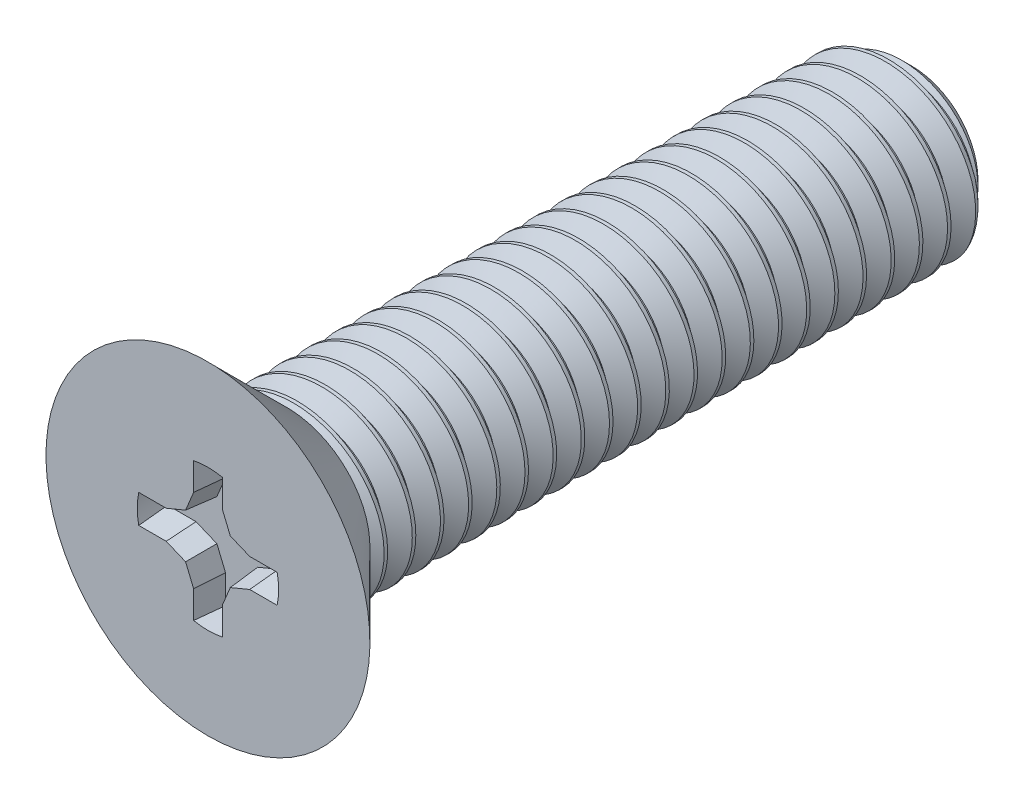
SolidWorks part; units mm, degrees
ref_plane "Front Plane" through (0, 0, 0) normal (0, 0, 1) x (1, 0, 0)
ref_plane "Top Plane" through (0, 0, 0) normal (0, 1, 0) x (1, 0, 0)
ref_plane "Right Plane" through (0, 0, 0) normal (1, 0, 0) x (0, 0, -1)
sketch "Sketch1" plane through (0, 0, 0) normal (1, 0, 0) x (0, 0, -1)
  line L0 (0, 0) -> (-2.5, 0) construction
  line L1 (-2.5, 4.6) -> (-2.5, -4.6) construction
  line L2 (-2.5, 4.6) -> (0, 2.1) construction
  line L3 (-2.5, -4.6) -> (0, -2.1) construction
  line L4 (0, 2.5) -> (0, -2.5) construction
  line L5 (0, 0) -> (17.5, 0) construction
  line L6 (0, 2.5) -> (0.8, 2.5) construction
  line L7 (0, 2.5) -> (-0.4, 2.5) construction
  line L8 (17.5, 2.1) -> (17.5, -2.1) construction
  point P6 (-2.5, 0)
  point P11 (0, 0)
  point P16 (-0.4, 2.5)
  point P17 (14.7, -2.5)
  point P20 (17.5, 0)
  point P21 (-1.25, 0)
  point P22 (14.7, -2.1)
  point P23 (17.5, -2.1)
  point P25 (17.5, 2.1)
  dimension "Head Height" = 2.5
  dimension "Head Diameter" = 9.2
  dimension "Countersink Angle" = 90
  dimension "Thread OD" = 5
  dimension "Length" = 20
  dimension "Thread Pitch" = 0.8
  dimension "D1" = 2.8
sketch "Sketch2" plane through (0, 0, 0) normal (0, 0, 1) x (1, 0, 0)
  line L0 (0.4064, 2.0066) -> (-0.4064, 2.0066) construction
  circle A0 centre (0, 0) radius 2.0066 construction
  point P3 (0, 2.0066)
  point P7 (0, 2.0066)
  dimension "Drive Dia" = 4.0132
  dimension "Drive Width" = 0.8128
sketch "Sketch3" plane through (0, 0, 0) normal (1, 0, 0) x (0, 0, -1)
  line L0 (-2.5, 0) -> (-2.5, 4.6)
  line L1 (-2.5, 4.6) -> (-0.4, 2.5)
  line L2 (-2.5, 4.6) -> (0, 2.1) construction
  line L3 (0, 2.5) -> (0.8, 2.5) construction
  line L4 (-2.5, 0) -> (-0.4, 0)
  line L5 (0, 0) -> (-2.5, 0) construction
  line L6 (-0.4, 0) -> (-0.4, 2.5)
revolve "Revolve1" add sketch "Sketch3" angle 360 about L4
sketch "Sketch5" plane through (0, 0, 0) normal (1, 0, 0) x (0, 0, -1)
  line L0 (17.5, 0) -> (-0.4, 0)
  line L1 (0, 0) -> (17.5, 0) construction
  line L2 (-0.4, 0) -> (-0.4, 2.5)
  line L3 (-0.4, 2.5) -> (16.868, 2.5)
  line L4 (16.868, 2.5) -> (17.5, 1.868)
  line L5 (17.5, 1.868) -> (17.5, 0)
  line L6 (16.868, 2.5) -> (17.5, 2.5) construction
  line L7 (17.5, 2.5) -> (17.5, 1.868) construction
  line L8 (0, 2.5) -> (0.8, 2.5) construction
  line L9 (-0.4, -2.5) -> (-0.4, 2.5) construction
  dimension "D1" = 0.632
revolve "Revolve2" add sketch "Sketch5" angle 360 about L0
sketch "Sketch4" plane through (0, 0, 2.5) normal (0, 0, 1) x (1, 0, 0)
  line L0 (0, 0) -> (0, 2.0066)
  line L1 (0, 0) -> (2.0066, 0)
  line L2 (0, 0) -> (1.1857, 1.1857) construction
  line L3 (0.4064, 1.965) -> (0.4064, 1.1857)
  line L4 (0.4064, 1.1857) -> (0.4064, 0.4064) construction
  line L5 (1.1857, 0.4064) -> (0.4064, 0.4064) construction
  line L6 (1.965, 0.4064) -> (1.1857, 0.4064)
  line L7 (0.4064, 1.1857) -> (0.6347, 0.6347)
  line L8 (0.6347, 0.6347) -> (1.1857, 0.4064)
  line L9 (0, 2.0066) -> (0, 4.6) construction
  line L10 (0, 4.6) -> (0, -4.6) construction
  circle A0 centre (0, 0) radius 2.0066 construction
  arc A1 (0, 2.0066) -> (0.4064, 1.965) centre (0, 0) cw
  arc A2 (2.0066, 0) -> (1.965, 0.4064) centre (0, 0) ccw
  arc A3 (1.1857, 0.4064) -> (0.4064, 1.1857) centre (1.1857, 1.1857) cw construction
  circle A4 centre (0, 0) radius 4.6 construction
  point P8 (0.6347, 0.6347)
  point P22 (0, -2.0066)
  point P23 (0, 2.0066)
  dimension "D1" = 2.5934
extrude "Cut-Extrude1" cut sketch "Sketch4" against normal blind 0.8333 contours L1 A2 L6 L8 L7 L3 A1 L0
pattern_circular "CirPattern1" count 4 over 360 about axis through (0, 0, 0) along (0, 0, 1) of "Cut-Extrude1"
draft "Draft2" type of draft neutral plane draft angle 5 faces to draft 16 face at (-1.5754, 0.4064, 2.0833) face at (-0.9102, 0.5205, 2.0833) face at (-0.5205, 0.9102, 2.0833) face at (-0.4064, 1.5754, 2.0833) face at (0.4064, 1.5754, 2.0833) face at (0.5205, 0.9102, 2.0833) face at (0.9102, 0.5205, 2.0833) face at (1.5754, 0.4064, 2.0833) face at (1.5754, -0.4064, 2.0833) face at (0.9102, -0.5205, 2.0833) face at (0.5205, -0.9102, 2.0833) face at (0.4064, -1.5754, 2.0833) face at (-0.4064, -1.5754, 2.0833) face at (-0.5205, -0.9102, 2.0833) face at (-0.9102, -0.5205, 2.0833) face at (-1.5754, -0.4064, 2.0833) neutral plane through (0, 0, 2.5) neutral plane normal (0, 0, 1) parameters "D1"=5
ref_plane "Plane1" through (0, 0, 0.4) normal (0, 0, -1) x (-1, 0, 0)
split "Split1" trim tools "Plane1" bodies to split 107 105 resulting bodies 108 109
sketch "Sketch6" plane through (0, 0, -17.5) normal (0, 0, 1) x (1, 0, 0)
  circle A1 centre (0, 0) radius 2.5
  circle A2 centre (0, 0) radius 2.5
  dimension "D1" = 0
curve "Helix/Spiral1" pitch 0.8 height 20 turns 25
sketch "Sketch7" plane through (0, 0, 0) normal (1, 0, 0) x (0, 0, -1)
  line L0 (17.45, 2.5866) -> (18.25, 2.5866) construction
  line L1 (17.45, 2.5866) -> (17.85, 1.8938) construction
  line L2 (17.85, 1.8938) -> (18.25, 2.5866) construction
  line L3 (17.8, 1.9804) -> (17.9, 1.9804) construction
  line L4 (17.5, 2.5) -> (18.2, 2.5) construction
  line L5 (17.85, 2.5) -> (17.85, 2.5866) construction
  line L6 (17.85, 1.9804) -> (17.85, 1.8938) construction
  line L7 (17.85, 2.5433) -> (17.475, 2.5433) construction
  line L10 (17.9, 1.9804) -> (17.8, 1.9804)
  line L11 (17.475, 2.5433) -> (17.8, 1.9804)
  line L12 (17.475, 2.5433) -> (18.225, 2.5433)
  line L13 (18.225, 2.5433) -> (17.9, 1.9804)
  dimension "D1" = 0.8
  dimension "D2" = 0.1
sweep "Cut-Sweep1" cut profiles "Sketch7" path "Helix/Spiral1" align with end faces yes
combine bodies "Combine1" operation type add bodies to combine 109 110
ref_plane "Plane2" through (0, 0, 0.4) normal (0, 0, 1) x (1, 0, 0)
sketch "Sketch8" plane through (0, 0, 0.4) normal (0, 0, 1) x (1, 0, 0)
  circle A0 centre (0, 0) radius 2.5
extrude "Boss-Extrude1" add sketch "Sketch8" against normal up to vertex (0.4 mm away) draft 45 up to point (0, 2.1, 0)
equation "\"D1@Sketch5\" = \"Thread Pitch@Sketch1\" * .79"
equation "\"D4@Helix/Spiral1\" = \"Thread Pitch@Sketch1\""
equation "\"D3@Helix/Spiral1\"=\"Length@Sketch1\""
equation "\"D1@Sketch7\" = \"Thread Pitch@Sketch1\""
equation "\"D2@Sketch7\" = \"Thread Pitch@Sketch1\" / 8"
equation "\"D1@Sketch1\"=\"Thread Pitch@Sketch1\"*3.5"
equation "\"D1@Cut-Extrude1\"=\"Head Height@Sketch1\"/3"
